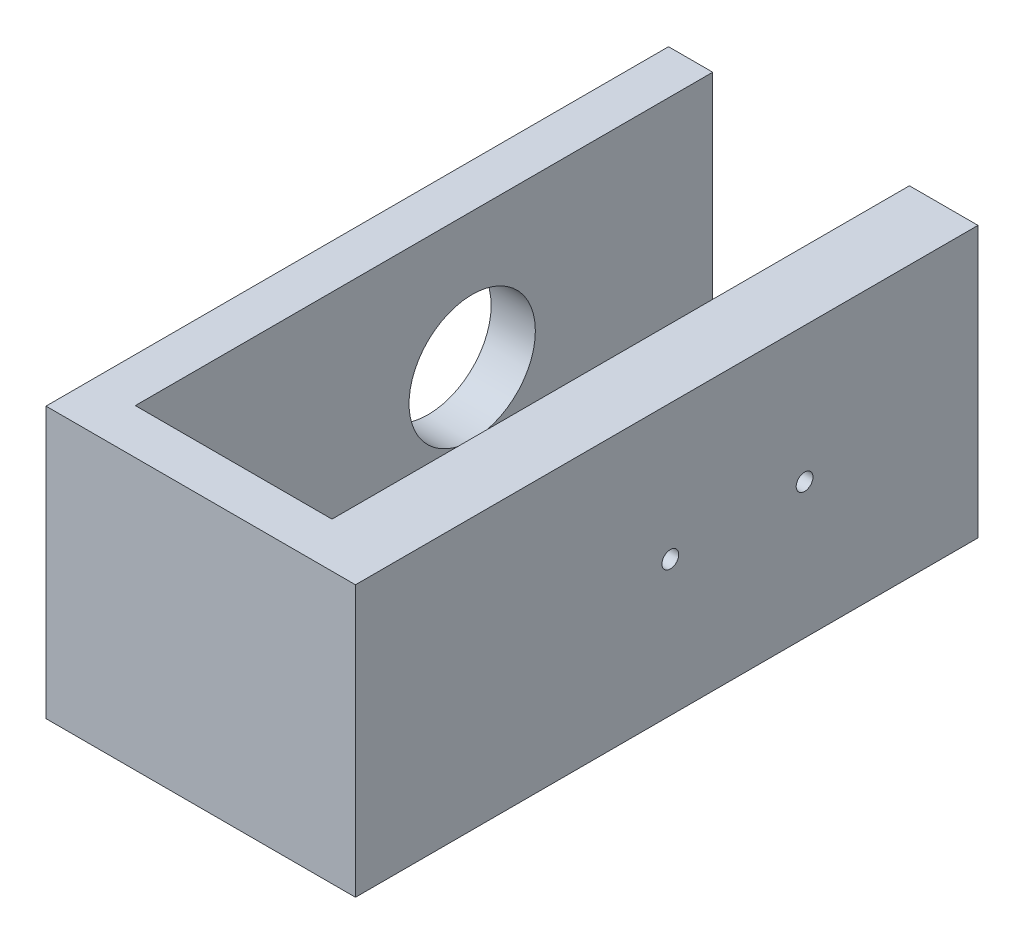
SolidWorks part; units mm, degrees
ref_plane "Front" through (0, 0, 0) normal (0, 0, 1) x (1, 0, 0)
ref_plane "Top" through (0, 0, 0) normal (0, 1, 0) x (1, 0, 0)
ref_plane "Right" through (0, 0, 0) normal (1, 0, 0) x (0, 0, -1)
sketch "Sketch1" plane through (0, 0, 0) normal (0, 1, 0) x (1, 0, 0)
  line L1 (0, 0) -> (5, 0)
  line L2 (0, 0) -> (0, 75)
  line L3 (0, 75) -> (5, 75)
  line L4 (5, 0) -> (5, 75)
  line L5 (0, 0) -> (50, 0)
  line L6 (0, 0) -> (0, 5)
  line L7 (0, 5) -> (50, 5)
  line L8 (50, 0) -> (50, 5)
  line L9 (50, 0) -> (45, 0)
  line L10 (50, 0) -> (50, 75)
  line L11 (50, 75) -> (45, 75)
  line L12 (45, 0) -> (45, 75)
  dimension "D1" = 40
  dimension "D2" = 5
  dimension "D3" = 5
  dimension "D4" = 5
  dimension "D5" = 75
extrude "Boss-Extrude1" add sketch "Sketch1" along normal blind 30 contours L2 L7 L4 L3 | L5 L12 L7 L4 | L7 L2 L1 L4 | L12 L7 L10 L11 | L12 L5 L8 L7 region at (2.5, 0, -2.5) region at (25, 0, -2.5) region at (2.5, 0, -40) region at (47.5, 0, -2.5) region at (47.5, 0, -40)
sketch "Sketch2" plane through (50, 0, 0) normal (1, 0, 0) x (0, 0, -1)
  line L0 (0, 30) -> (0, 0) construction
  line L1 (0, 30) -> (75, 30) construction
  circle A0 centre (48.34, 15) radius 7
  dimension "D1" = 14
  dimension "D2" = 48.34
  dimension "D3" = 15
extrude "Cut-Extrude1" cut sketch "Sketch2" against normal blind 70
sketch "Sketch3" plane through (50, 0, 0) normal (1, 0, 0) x (0, 0, -1)
  line L1 (-17.949, 35.7713) -> (93.2187, 35.7713)
  line L2 (-17.949, 35.7713) -> (-17.949, -4.9755)
  line L3 (-17.949, -4.9755) -> (93.2187, -4.9755)
  line L4 (93.2187, 35.7713) -> (93.2187, -4.9755)
extrude "Cut-Extrude2" cut sketch "Sketch3" against normal blind 0.8
sketch "Sketch5" plane through (0, 0, 0) normal (-1, 0, 0) x (0, 0, 1)
  line L1 (5.7432, -79.916) -> (-112.0315, -79.916)
  line L2 (5.7432, -79.916) -> (5.7432, 78.3758)
  line L3 (5.7432, 78.3758) -> (-112.0315, 78.3758)
  line L4 (-112.0315, -79.916) -> (-112.0315, 78.3758)
extrude "Cut-Extrude3" cut sketch "Sketch5" against normal blind 0.8
sketch "Sketch6" plane through (45, 0, 0) normal (-1, 0, 0) x (0, 0, 1)
  line L1 (-75, 0) -> (-5, 0)
  line L2 (-75, 0) -> (-75, 30)
  line L3 (-75, 30) -> (-5, 30)
  line L4 (-5, 0) -> (-5, 30)
extrude "Boss-Extrude2" add sketch "Sketch6" along normal blind 3.4
sketch "Sketch7" plane through (5, 0, 0) normal (1, 0, 0) x (0, 0, -1)
  line L1 (75, 30) -> (5, 30)
  line L2 (75, 30) -> (75, 0)
  line L3 (75, 0) -> (5, 0)
  line L4 (5, 30) -> (5, 0)
extrude "Boss-Extrude3" add sketch "Sketch7" along normal blind 6.7
sketch "Sketch8" plane through (0.8, 0, 0) normal (-1, 0, 0) x (0, 0, 1)
  line L1 (-75.0605, -16.6107) -> (8.7027, -16.6107)
  line L2 (-75.0605, -16.6107) -> (-75.0605, 61.3062)
  line L3 (-75.0605, 61.3062) -> (8.7027, 61.3062)
  line L4 (8.7027, -16.6107) -> (8.7027, 61.3062)
extrude "Cut-Extrude5" cut sketch "Sketch8" against normal blind 6 contours L1 L4 L3 L2
sketch "Sketch9" plane through (45, 0, 0) normal (1, 0, 0) x (0, 0, -1)
  circle A0 centre (48.34, 15) radius 7
extrude "Cut-Extrude6" cut sketch "Sketch9" against normal through all
sketch "Sketch10" plane through (0, 0, -5) normal (0, 0, -1) x (-1, 0, 0)
  line L5 (-41.6, 30) -> (-11.7, 30)
  line L6 (-41.6, 30) -> (-41.6, 0)
  line L7 (-41.6, 0) -> (-11.7, 0)
  line L8 (-11.7, 30) -> (-11.7, 0)
extrude "Boss-Extrude4" add sketch "Sketch10" along normal blind 6
sketch "Sketch11" plane through (0, 0, 0) normal (0, 0, 1) x (1, 0, 0)
  line L1 (55.9671, -15.4127) -> (0, -15.4127)
  line L2 (55.9671, -15.4127) -> (55.9671, 46.8172)
  line L3 (55.9671, 46.8172) -> (0, 46.8172)
  line L4 (0, -15.4127) -> (0, 46.8172)
extrude "Cut-Extrude7" cut sketch "Sketch11" against normal blind 6
sketch "Sketch12" plane through (11.7, 0, 0) normal (1, 0, 0) x (0, 0, -1)
  line L1 (75, 30) -> (11, 30)
  line L2 (75, 30) -> (75, 0)
  line L3 (75, 0) -> (11, 0)
  line L4 (11, 30) -> (11, 0)
extrude "Boss-Extrude6" add sketch "Sketch12" along normal blind 4.05
sketch "Sketch13" plane through (6.8, 0, 0) normal (-1, 0, 0) x (0, 0, 1)
  line L1 (-6.1392, -45.1493) -> (-91.7571, -45.1493)
  line L2 (-6.1392, -45.1493) -> (-6.1392, 78.234)
  line L3 (-6.1392, 78.234) -> (-91.7571, 78.234)
  line L4 (-91.7571, -45.1493) -> (-91.7571, 78.234)
extrude "Cut-Extrude9" cut sketch "Sketch13" against normal blind 4.05
sketch "Sketch15" plane through (6.8, 0, 0) normal (-1, 0, 0) x (0, 0, 1)
  line L1 (19.9907, -73.0758) -> (-19.0586, -73.0758)
  line L2 (19.9907, -73.0758) -> (19.9907, 78.5563)
  line L3 (19.9907, 78.5563) -> (-19.0586, 78.5563)
  line L4 (-19.0586, -73.0758) -> (-19.0586, 78.5563)
extrude "Cut-Extrude10" cut sketch "Sketch15" against normal blind 3.95
sketch "Sketch16" plane through (15.75, 0, 0) normal (1, 0, 0) x (0, 0, -1)
  line L1 (75, 30) -> (11, 30)
  line L2 (75, 30) -> (75, 0)
  line L3 (75, 0) -> (11, 0)
  line L4 (11, 30) -> (11, 0)
extrude "Boss-Extrude7" add sketch "Sketch16" along normal blind 4.05
sketch "Sketch17" plane through (10.85, 0, 0) normal (-1, 0, 0) x (0, 0, 1)
  line L1 (5.5634, -40.7136) -> (-90.9107, -40.7136)
  line L2 (5.5634, -40.7136) -> (5.5634, 63.8526)
  line L3 (5.5634, 63.8526) -> (-90.9107, 63.8526)
  line L4 (-90.9107, -40.7136) -> (-90.9107, 63.8526)
extrude "Cut-Extrude11" cut sketch "Sketch17" against normal blind 4.05
sketch "Sketch18" plane through (10.75, 0, 0) normal (-1, 0, 0) x (0, 0, 1)
  line L1 (-2.613, -16.3996) -> (-9.3682, -16.3996)
  line L2 (-2.613, -16.3996) -> (-2.613, 38.6596)
  line L3 (-2.613, 38.6596) -> (-9.3682, 38.6596)
  line L4 (-9.3682, -16.3996) -> (-9.3682, 38.6596)
extrude "Cut-Extrude12" cut sketch "Sketch18" against normal blind 4.05
sketch "Sketch19" plane through (19.8, 0, 0) normal (1, 0, 0) x (0, 0, -1)
  circle A0 centre (48.34, 15) radius 7
extrude "Cut-Extrude14" cut sketch "Sketch19" against normal blind 34.05 contours A0
sketch "Sketch23" plane through (49.2, 0, 0) normal (1, 0, 0) x (0, 0, -1)
  line L5 (36.6918, 25.8756) -> (56.5414, 25.8756)
  line L6 (36.6918, 25.8756) -> (36.6918, 6.0204)
  line L7 (36.6918, 6.0204) -> (56.5414, 6.0204)
  line L8 (56.5414, 25.8756) -> (56.5414, 6.0204)
extrude "Boss-Extrude9" add sketch "Sketch23" against normal blind 4.2
sketch "Sketch24" plane through (49.2, 0, 0) normal (1, 0, 0) x (0, 0, -1)
  line L0 (6, 30) -> (75, 30) construction
  line L1 (75, 0) -> (75, 30) construction
  circle A0 centre (48.34, 15) radius 7.44
  circle A1 centre (55.78, 15) radius 0.93
  circle A2 centre (40.9, 15) radius 0.93
  point P12 (48.34, 15)
  dimension "D1" = 14.88
  dimension "D2" = 15
  dimension "D4" = 2
  dimension "D3" = 26.66
extrude "Cut-Extrude16" cut sketch "Sketch24" against normal blind 4 contours A1
extrude "Cut-Extrude17" cut sketch "Sketch24<5>" against normal blind 4 contours A2
sketch "Sketch24<5>" plane through (49.2, 0, 0) normal (1, 0, 0) x (0, 0, -1) same geometry as "Sketch24"
sketch "Sketch26" plane through (45, 0, 0) normal (-1, 0, 0) x (0, 0, 1)
  circle A0 centre (-48.34, 15) radius 7
extrude "Cut-Extrude18" cut sketch "Sketch26" against normal blind 0.4 contours A0
